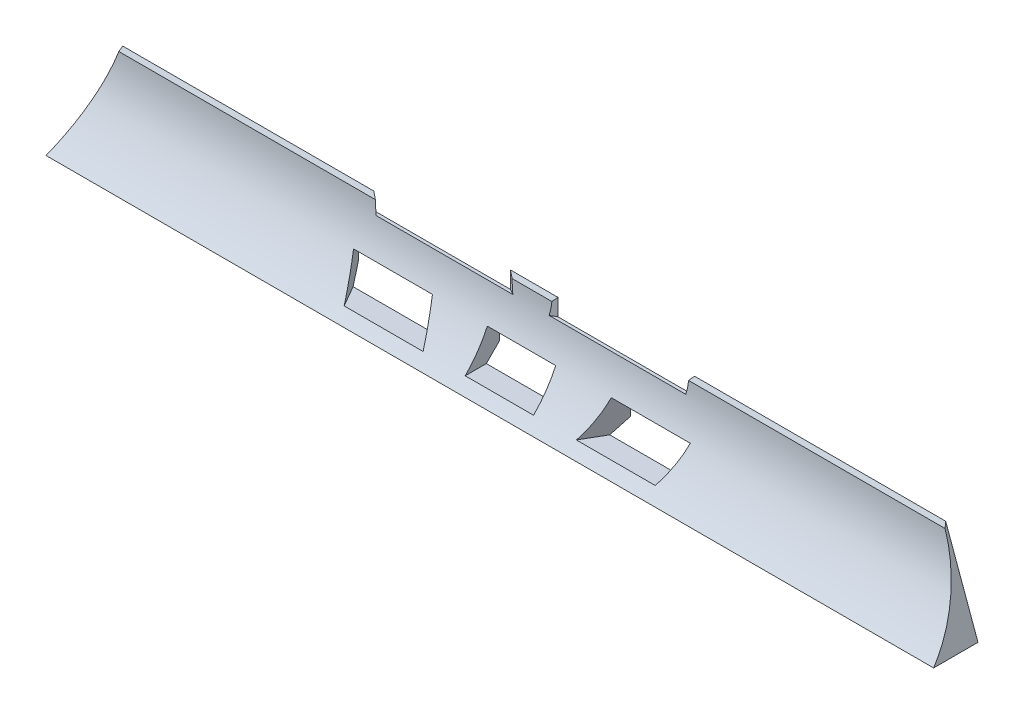
SolidWorks part; units mm, degrees
material "ABS"
ref_plane "Front Plane" through (0, 0, 0) normal (0, 0, 1) x (1, 0, 0)
ref_plane "Top Plane" through (0, 0, 0) normal (0, 1, 0) x (1, 0, 0)
ref_plane "Right Plane" through (0, 0, 0) normal (1, 0, 0) x (0, 0, -1)
sketch "Sketch1" plane through (0, 0, 0) normal (1, 0, 0) x (0, 0, -1)
  line L0 (0, 0) -> (-10, 0)
  line L1 (-10, 0) -> (0, 20)
  line L2 (0, 20) -> (0, 0)
  dimension "D1" = 10
  dimension "D2" = 20
extrude "Boss-Extrude1" add sketch "Sketch1" along normal blind 200
sketch "Sketch2" plane through (200, 0, 0) normal (1, 0, 0) x (0, 0, -1)
  line L0 (0, 20) -> (-10, 0) construction
  line L1 (-10, 0) -> (0, 0) construction
  line L2 (0, 0) -> (0, 20) construction
  line L3 (-10, 0) -> (-0.5, 19)
  arc A0 (-10, 0) -> (-0.5, 19) centre (-25.4923, 19.6211) ccw
  dimension "D3" = 25
  dimension "D1" = 0
  dimension "D2" = 0.5
extrude "Cut-Extrude1" cut sketch "Sketch2" against normal through all
sketch "Sketch4" plane through (200, 0, 0) normal (1, 0, 0) x (0, 0, -1)
  line L0 (-5, 0) -> (0, 5)
  line L1 (-10, 0) -> (0, 0) construction
  line L2 (0, 0) -> (0, 20) construction
  line L3 (0, 5) -> (0, 0)
  line L4 (0, 0) -> (-5, 0)
  dimension "D1" = 5
  dimension "D2" = 5
extrude "Cut-Extrude2" cut sketch "Sketch4" against normal through all
sketch "Sketch5" plane through (0, 0, 0) normal (0, 0, -1) x (-1, 0, 0)
  line L0 (0, 0) -> (-200, 0) construction
  line L1 (-200, 5) -> (-197, 5)
  line L2 (-200, 5) -> (-200, 0)
  line L3 (-200, 0) -> (-197, 0)
  line L4 (-197, 5) -> (-197, 0)
  dimension "D1" = 3
extrude "Boss-Extrude2" add sketch "Sketch5" against normal up to surface up to face at (100, 2.5, 2.5)
ref_plane "Plane1" through (100, 0, 0) normal (1, 0, 0) x (0, 0, -1)
sketch "Sketch6" plane through (0, 0, 0) normal (0, 0, -1) x (-1, 0, 0)
  line L0 (-200, 20) -> (-192.7206, 20)
  line L1 (-200, 20) -> (0, 20) construction
  line L2 (-192.7206, 20) -> (-200, 0)
  line L3 (-200, 20) -> (-200, 0)
  dimension "D1" = 20
extrude "Cut-Extrude3" cut sketch "Sketch6" against normal through all
mirror "Mirror2" about plane through (100, 0, 0) normal (1, 0, 0) of "Cut-Extrude3", "Boss-Extrude2"
sketch "Sketch7" plane through (0, 0, 0) normal (0, 0, -1) x (-1, 0, 0)
  line L1 (-159.8316, 11) -> (-167.8316, 11)
  line L2 (-159.8316, 11) -> (-159.8316, 0)
  line L3 (-159.8316, 0) -> (-167.8316, 0)
  line L4 (-167.8316, 11) -> (-167.8316, 0)
  line L5 (-160.8316, 11) -> (-166.8316, 11) construction
  line L6 (-166.8316, 0) -> (-160.8316, 0) construction
  line L7 (-166.8316, 11) -> (-166.8316, 0) construction
  dimension "D1" = 8
  dimension "D2" = 1
extrude "Boss-Extrude3" add sketch "Sketch7" against normal up to next
sketch "Sketch8" plane through (0, 0, 0) normal (0, 0, -1) x (-1, 0, 0)
  line L1 (-165.5637, 8.5) -> (-167.2957, 5.5)
  line L2 (-167.2957, 5.5) -> (-165.5637, 2.5)
  line L3 (-165.5637, 2.5) -> (-162.0995, 2.5)
  line L4 (-162.0995, 2.5) -> (-160.3675, 5.5)
  line L5 (-160.3675, 5.5) -> (-162.0995, 8.5)
  line L6 (-162.0995, 8.5) -> (-165.5637, 8.5)
  line L7 (-167.8316, 0) -> (-159.8316, 0) construction
  line L8 (-165.3316, 8) -> (-165.3316, 3) construction
  circle A2 centre (-163.8316, 5.5) radius 3 construction
  point P13 (-163.8316, 8.5)
  dimension "D1" = 6
  dimension "D2" = 1.5
  dimension "D3" = 5.5
extrude "Cut-Extrude4" cut sketch "Sketch8" against normal blind 1.8 contours L5 L6 L1 L2 L3 L4 | L1 L2 L3 L4 L5 L6 region at (163.8316, 5.5, 0)
mirror "Mirror3" about plane through (100, 0, 0) normal (1, 0, 0) of "Cut-Extrude4", "Boss-Extrude3"
sketch "Sketch9" plane through (0, 0, 0) normal (0, 0, 1) x (1, 0, 0)
  line L1 (92.2158, 2) -> (107.6158, 2)
  line L2 (92.2158, 2) -> (92.2158, 9.2)
  line L3 (92.2158, 9.2) -> (107.6158, 9.2)
  line L4 (107.6158, 2) -> (107.6158, 9.2)
extrude "Cut-Extrude6" cut sketch "Sketch9" along normal through all
ref_plane "Plane2" through (32.136, 0, -55.6612) normal (-0.5, 0, 0.866) x (0.866, 0, 0.5)
sketch "Sketch10" plane through (32.136, 0, -55.6612) normal (-0.5, 0, 0.866) x (0.866, 0, 0.5)
  line L1 (105.439, 2) -> (120.839, 2)
  line L2 (105.439, 2) -> (105.439, 9.2)
  line L3 (105.439, 9.2) -> (120.839, 9.2)
  line L4 (120.839, 2) -> (120.839, 9.2)
extrude "Cut-Extrude8" cut sketch "Sketch10" along normal blind 15.8 and the other way blind 6.8
ref_plane "Plane3" through (115.6697, 0, -66.7819) normal (-0.866, 0, 0.5) x (0.5, 0, 0.866)
sketch "Sketch11" plane through (115.6697, 0, -66.7819) normal (-0.866, 0, 0.5) x (0.5, 0, 0.866)
  line L1 (68.0717, 25) -> (52.6717, 25)
  line L2 (68.0717, 25) -> (68.0717, 16.2)
  line L3 (68.0717, 16.2) -> (52.6717, 16.2)
  line L4 (52.6717, 25) -> (52.6717, 16.2)
  line L7 (52.6717, 25) -> (52.6717, 17.8) construction
  line L8 (47.1217, 16.2) -> (73.6217, 16.2) construction
extrude "Cut-Extrude9" cut sketch "Sketch11" along normal blind 97.8
mirror "Mirror4" about plane through (100, 0, 0) normal (1, 0, 0) of "Cut-Extrude8", "Cut-Extrude9"
